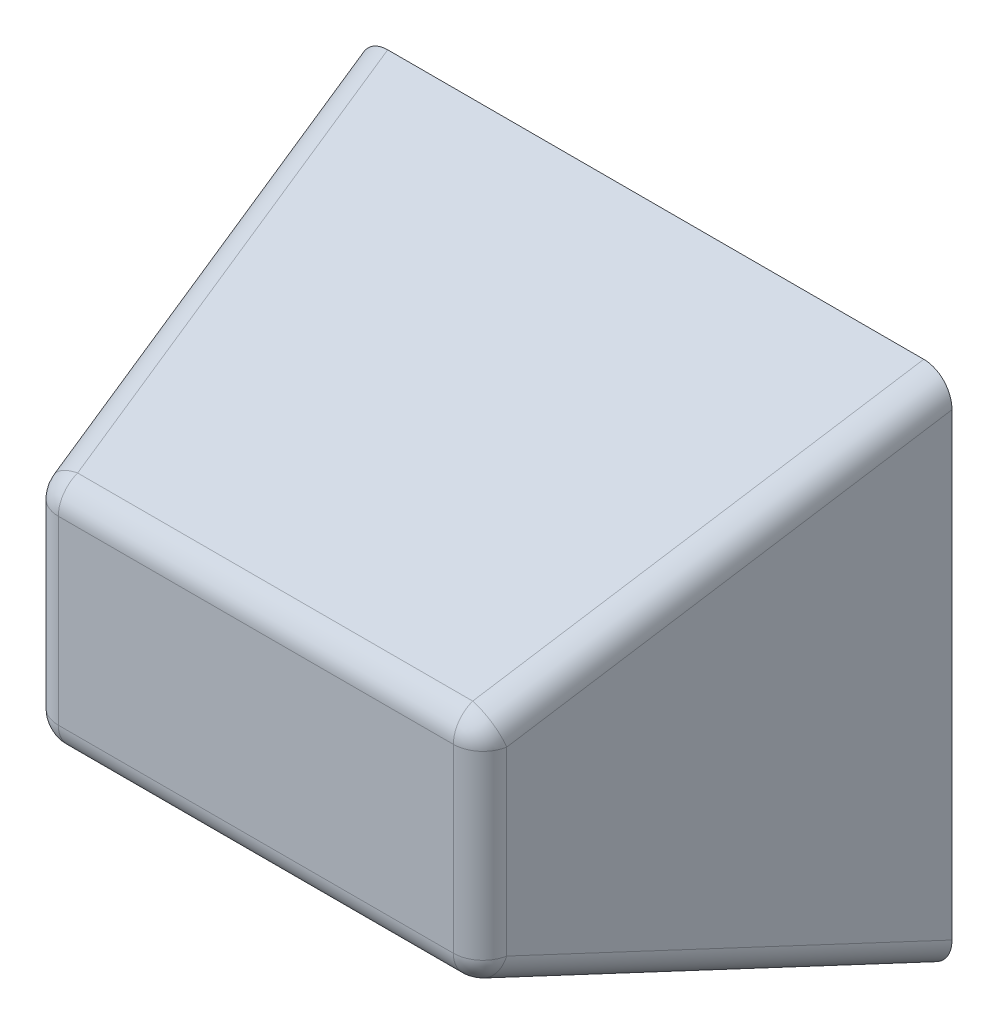
SolidWorks part; units mm, degrees
material "Polyurethane Foam Flexible"
ref_plane "Front Plane" through (0, 0, 0) normal (0, 0, 1) x (1, 0, 0)
ref_plane "Top Plane" through (0, 0, 0) normal (0, 1, 0) x (1, 0, 0)
ref_plane "Right Plane" through (0, 0, 0) normal (1, 0, 0) x (0, 0, -1)
sketch "Sketch1" plane through (0, 0, 0) normal (0, 0, 1) x (1, 0, 0)
  line L1 (-200, 175) -> (200, 175)
  line L2 (-200, 175) -> (-200, -175)
  line L3 (-200, -175) -> (200, -175)
  line L4 (200, 175) -> (200, -175)
  line L5 (-200, 175) -> (200, -175) construction
  line L6 (-200, -175) -> (200, 175) construction
  point P0 (0, 0)
  dimension "D1" = 400
  dimension "D2" = 350
ref_plane "Plane1" through (0, 0, 270) normal (0, 0, 1) x (1, 0, 0)
sketch "Sketch2" plane through (0, 0, 270) normal (0, 0, 1) x (1, 0, 0)
  line L1 (-150, 75) -> (150, 75)
  line L2 (-150, 75) -> (-150, -75)
  line L3 (-150, -75) -> (150, -75)
  line L4 (150, 75) -> (150, -75)
  line L5 (-150, 75) -> (150, -75) construction
  line L6 (-150, -75) -> (150, 75) construction
  point P0 (0, 0)
  dimension "D1" = 300
  dimension "D2" = 150
loft "Loft1" add profiles "Sketch2", "Sketch1" connector at (-150, 75, 270) connector at (-200, 175, 0)
fillet "Fillet1" radius 20 8 edges
